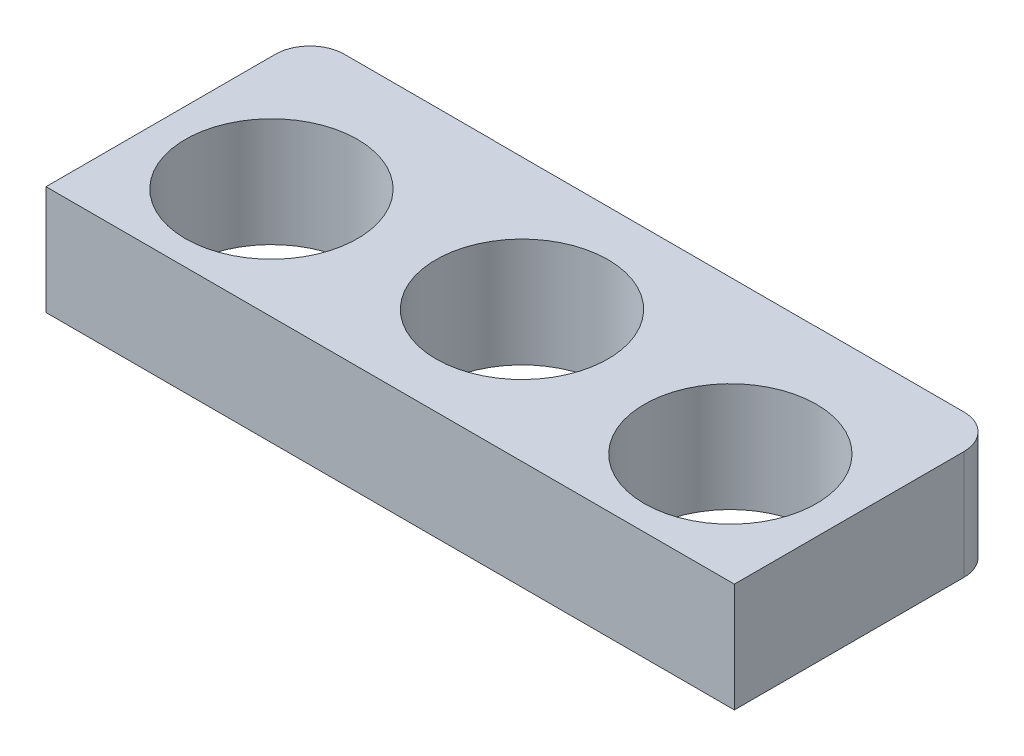
SolidWorks part; units mm, degrees
ref_plane "前视基准面" through (0, 0, 0) normal (0, 0, 1) x (1, 0, 0)
ref_plane "上视基准面" through (0, 0, 0) normal (0, 1, 0) x (1, 0, 0)
ref_plane "右视基准面" through (0, 0, 0) normal (1, 0, 0) x (0, 0, -1)
sketch "草图1" plane through (0, 0, 0) normal (0, 1, 0) x (1, 0, 0)
  line L1 (0, 0) -> (0, -15) construction
  line L2 (0, 0) -> (-30, 0)
  line L4 (-30, 0) -> (-30, 23)
  line L5 (-30, 23) -> (-14, 23)
  line L6 (-14, 23) -> (-14, 22.9889)
  line L13 (-14, 22.9889) -> (14, 22.9889)
  line L14 (14, 22.9889) -> (14, 23)
  line L15 (14, 23) -> (30, 23)
  line L16 (30, 23) -> (30, 0)
  line L17 (30, 0) -> (0, 0)
  point P0 (0, 0)
  dimension "D1" = 30
  dimension "D3" = 23
  dimension "D4" = 16
extrude "凸台-拉伸1" add sketch "草图1" along normal blind 9.5
sketch "草图3" plane through (0, 9.5, 0) normal (0, 1, 0) x (1, 0, 0)
  line L1 (0, 0) -> (0, 22.9889) construction
  line L2 (14, 22.9889) -> (-14, 22.9889) construction
  line L3 (-30, 0) -> (30, 0) construction
  circle A0 centre (0, 11.4889) radius 7.5
  circle A1 centre (-20, 9.65) radius 7.5
  circle A2 centre (20, 9.65) radius 7.5
  dimension "D1" = 15
  dimension "D2" = 11.5
  dimension "D3" = 15
  dimension "D4" = 40
  dimension "D5" = 9.65
extrude "切除-拉伸2" cut sketch "草图3" against normal through all
fillet "圆角2" radius 3 4 edges at (30, 4.75, -23) (14, 4.75, -22.9889) (-14, 4.75, -22.9889) (-30, 4.75, -23)
ref_plane "基准面1" through (0, 4.5, 0) normal (0, 1, 0) x (1, 0, 0)
sketch "草图4" plane through (0, 4.5, 0) normal (0, 1, 0) x (1, 0, 0)
  line L0 (9, 22.9889) -> (9, 0) construction
  line L1 (13.7418, 22.9889) -> (-13.7418, 22.9889) construction
  line L2 (-30, 0) -> (30, 0) construction
  line L3 (-9, 22.9889) -> (-9, 0) construction
  line L4 (-30, 20) -> (-30, 0) construction
  line L5 (30, 0) -> (30, 20) construction
  dimension "D1" = 21
  dimension "D2" = 21
